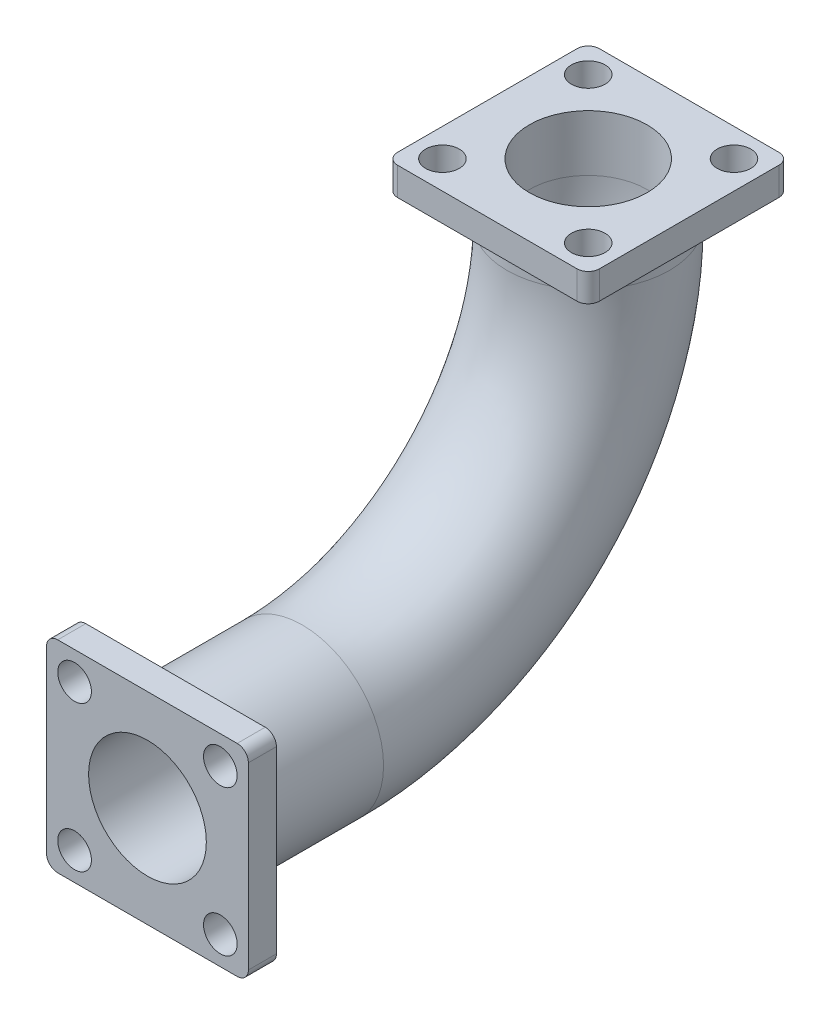
SolidWorks part; units mm, degrees
ref_plane "Front Plane" through (0, 0, 0) normal (0, 0, 1) x (1, 0, 0)
ref_plane "Top Plane" through (0, 0, 0) normal (0, 1, 0) x (1, 0, 0)
ref_plane "Right Plane" through (0, 0, 0) normal (1, 0, 0) x (0, 0, -1)
sketch "Sketch1" plane through (0, 0, 0) normal (1, 0, 0) x (0, 0, -1)
  line L0 (0, 0) -> (0, -100)
  line L1 (-510, -610) -> (-786.0825, -610)
  arc A0 (-510, -610) -> (0, -100) centre (-510, -100) ccw
  point P6 (0, -610)
  dimension "D2" = 510
  dimension "D1" = 610
sketch "Sketch4" plane through (0, 0, 0) normal (0, 1, 0) x (1, 0, 0)
  circle A0 centre (0, 0) radius 105
  circle A1 centre (0, 0) radius 145
  dimension "D1" = 210
  dimension "D2" = 290
sweep "Sweep1" add profiles "Sketch4" path "Sketch1"
sketch "Sketch6" plane through (0, 0, 0) normal (0, 1, 0) x (1, 0, 0)
  line L0 (130, 193.0111) -> (130, -211.4771) construction
  line L1 (160, 180) -> (-160, 180)
  line L2 (180, 160) -> (180, -160)
  line L3 (160, -180) -> (-160, -180)
  line L4 (-180, 160) -> (-180, -160)
  line L5 (180, 180) -> (-180, -180) construction
  line L6 (180, -180) -> (-180, 180) construction
  line L7 (-130, 203.2893) -> (-130, -215.568) construction
  line L8 (-212.4816, -140.7768) -> (-230.4429, -130)
  circle A0 centre (130, 130) radius 30
  circle A1 centre (-130, 130) radius 30
  circle A4 centre (-130, 130) radius 15
  circle A5 centre (130, 130) radius 15
  circle A8 centre (-130, -130) radius 30
  circle A9 centre (-130, -130) radius 15
  circle A10 centre (130, -130) radius 30
  circle A11 centre (130, -130) radius 15
  arc A12 (180, -160) -> (160, -180) centre (160, -160) cw
  arc A13 (-160, -180) -> (-180, -160) centre (-160, -160) cw
  arc A14 (160, 180) -> (180, 160) centre (160, 160) cw
  arc A15 (-160, 180) -> (-180, 160) centre (-160, 160) ccw
  circle A16 centre (0, 0) radius 105
  point P0 (0, 0)
  circle M8 centre (0, 0) radius 145
  dimension "D5" = 30
  dimension "D3" = 60
  dimension "D7" = 20
  dimension "D1" = 360
  dimension "D2" = 360
  dimension "D4" = 50
extrude "Boss-Extrude3" add sketch "Sketch6" against normal blind 50 contours L1 A15 L4 A13 L3 A12 L2 A14 A0 A1 A8 A10 M8 region at (170.5421, 0, -170.5421)
fillet "Fillet1" radius 10 1 edges at (0, -50, 145)
sketch "Sketch7" plane through (0, 0, 786.0825) normal (0, 0, 1) x (1, 0, 0)
  line L1 (160, -430) -> (-160, -430)
  line L2 (180, -450) -> (180, -770)
  line L3 (160, -790) -> (-160, -790)
  line L4 (-180, -450) -> (-180, -770)
  line L5 (180, -430) -> (-180, -790) construction
  line L6 (180, -790) -> (-180, -430) construction
  line L8 (-237.4605, -480) -> (314.6891, -480) construction
  line L10 (314.6891, -740) -> (-224.8966, -740) construction
  circle A0 centre (-130, -480) radius 30
  circle A1 centre (-130, -480) radius 15
  circle A2 centre (130, -480) radius 30
  circle A3 centre (130, -480) radius 15
  circle A4 centre (-130, -740) radius 30
  circle A5 centre (-130, -740) radius 15
  circle A6 centre (130, -740) radius 30
  circle A7 centre (130, -740) radius 15
  circle A8 centre (0, -610) radius 105
  arc A9 (160, -430) -> (180, -450) centre (160, -450) cw
  arc A10 (180, -770) -> (160, -790) centre (160, -770) cw
  arc A11 (-160, -790) -> (-180, -770) centre (-160, -770) cw
  arc A12 (-160, -430) -> (-180, -450) centre (-160, -450) ccw
  point P0 (0, -610)
  circle M9 centre (0, -610) radius 145
  dimension "D3" = 20
  dimension "D1" = 360
  dimension "D2" = 360
  dimension "D6" = 50
extrude "Boss-Extrude5" add sketch "Sketch7" against normal blind 50 contours L1 A12 L4 A11 L3 A10 L2 A9 A0 A2 A4 A6 M9 region at (170.5421, -439.4579, 786.0825)
sketch "Sketch11" plane through (0, 0, 0) normal (1, 0, 0) x (0, 0, -1)
